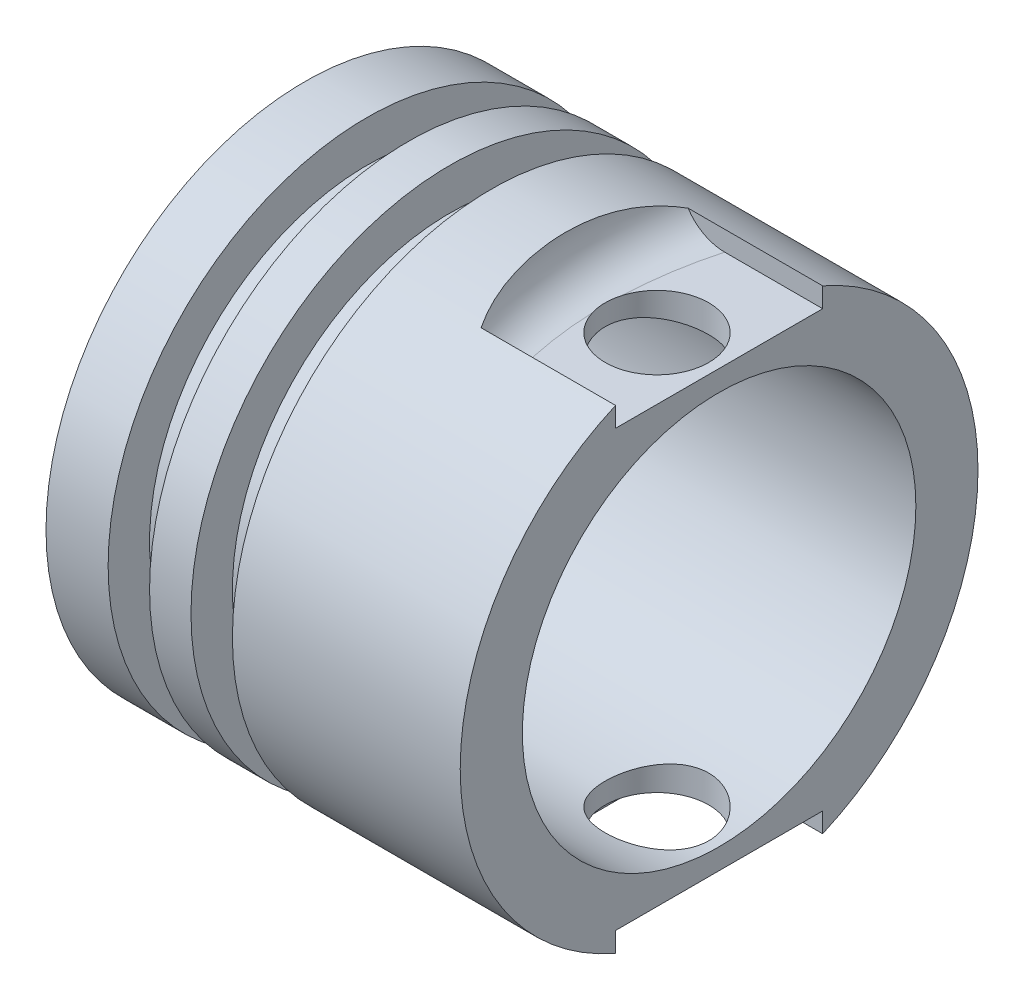
SolidWorks part; units mm, degrees
ref_plane "Front Plane" through (0, 0, 0) normal (0, 0, 1) x (1, 0, 0)
ref_plane "Top Plane" through (0, 0, 0) normal (0, 1, 0) x (1, 0, 0)
ref_plane "Right Plane" through (0, 0, 0) normal (1, 0, 0) x (0, 0, -1)
sketch "Sketch1" plane through (0, 0, 0) normal (0, 0, 1) x (1, 0, 0)
  line L0 (0, 0) -> (-1, 0)
  line L1 (-1, 0) -> (-1, 12.5)
  line L2 (-1, 12.5) -> (2, 12.5)
  line L3 (2, 12.5) -> (2, 10.5)
  line L4 (2, 10.5) -> (4, 10.5)
  line L5 (4, 10.5) -> (4, 12.5)
  line L6 (4, 12.5) -> (6, 12.5)
  line L7 (6, 12.5) -> (6, 10.5)
  line L8 (6, 10.5) -> (8, 10.5)
  line L9 (8, 10.5) -> (8, 12.5)
  line L10 (8, 12.5) -> (19, 12.5)
  line L11 (19, 12.5) -> (19, 9.5)
  line L12 (19, 9.5) -> (-0.0102, 9.5)
  line L13 (-0.0102, 9.5) -> (0, 0)
  dimension "D1" = 1
  dimension "D2" = 20
  dimension "D3" = 2
  dimension "D4" = 2
  dimension "D5" = 3
  dimension "D6" = 2
  dimension "D7" = 2
  dimension "D8" = 2
  dimension "D9" = 2
  dimension "D10" = 2
  dimension "D11" = 12.5
  dimension "D12" = 1
revolve "Revolve1" add sketch "Sketch1" angle 360 about L0
ref_plane "Plane2" through (0, 12.5, 0) normal (0, 1, 0) x (1, 0, 0)
sketch "Sketch4" plane through (0, 12.5, 0) normal (0, 1, 0) x (1, 0, 0)
  line L0 (21.0348, -5) -> (21.0348, 5)
  line L1 (21.0348, 5) -> (12.2034, 5)
  line L2 (21.0348, -5) -> (12.2034, -5)
  line L3 (0, 0) -> (21.0348, 0) construction
  arc A0 (12.2034, 5) -> (12.2034, -5) centre (32.4671, 0) ccw
  dimension "D1" = 10
extrude "Cut-Extrude2" cut sketch "Sketch4" against normal blind 2
fillet "Fillet1" radius 2 1 edges at (11.5956, 10.5, 0)
ref_plane "Plane3" through (0, -12.5, 0) normal (0, 1, 0) x (1, 0, 0)
sketch "Sketch6" plane through (0, -12.5, 0) normal (0, 1, 0) x (1, 0, 0)
  line L0 (19, -5) -> (12.5062, -5)
  line L1 (19, 5) -> (12.5062, 5)
  line L2 (19, -5) -> (19, 5)
  arc A0 (12.5062, -5) -> (12.5062, 5) centre (25.7791, 0) cw
extrude "Cut-Extrude3" cut sketch "Sketch6" along normal blind 2
fillet "Fillet2" radius 2 1 edges at (11.5956, -10.5, 0)
sketch "Sketch7" plane through (0, -12.5, 0) normal (0, 1, 0) x (1, 0, 0)
  line L0 (19, 5) -> (19, -5) construction
  circle A0 centre (16, 0) radius 2.5
  point P4 (19, 0)
  dimension "D1" = 5
  dimension "D2" = 3
extrude "Cut-Extrude4" cut sketch "Sketch7" along normal through all
